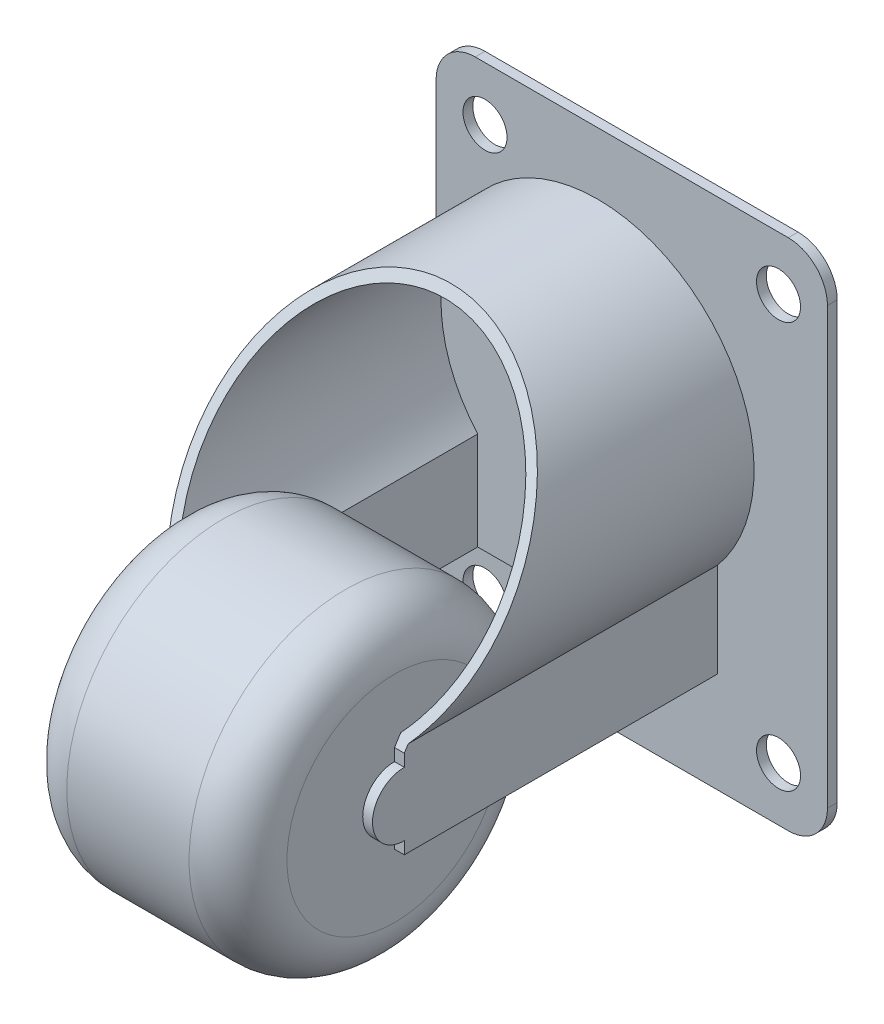
SolidWorks part; units mm, degrees
ref_plane "前视基准面" through (0, 0, 0) normal (0, 0, 1) x (1, 0, 0)
ref_plane "上视基准面" through (0, 0, 0) normal (0, 1, 0) x (1, 0, 0)
ref_plane "右视基准面" through (0, 0, 0) normal (1, 0, 0) x (0, 0, -1)
sketch "草图1" plane through (0, 0, 0) normal (0, 0, 1) x (1, 0, 0)
  line L0 (0, 0) -> (0, 20)
  line L1 (22.5, 39.8431) -> (22.5, 27.5869) construction
  line L2 (45, 0) -> (45, 20)
  line L3 (0, 0) -> (45, 0) construction
  arc A0 (0, 20) -> (45, 20) centre (22.5, 39.8431) cw
  point P7 (22.5, 69.8431)
  dimension "D1" = 30
  dimension "D2" = 45
  dimension "D3" = 20
extrude "拉伸-薄壁1" add sketch "草图1" along normal blind 62 thin thin type one direction wall 2
sketch "草图2" plane through (47, 0, 0) normal (1, 0, 0) x (0, 0, -1)
  line L1 (-62, 18) -> (-25, 76.4254)
  line L2 (-62, 0) -> (-62, 19.2579) construction
  line L7 (-25, 76.4254) -> (-62, 71.8431)
  line L8 (-62, 71.8431) -> (-62, 18)
  line L9 (-62, 0) -> (0, 0) construction
  line L10 (0, 19.2579) -> (0, 71.8431) construction
  point P7 (-29.9527, 57.8972)
  point P11 (-25, 76.4254)
  dimension "D1" = 18
  dimension "D2" = 25
extrude "切除-拉伸1" cut sketch "草图2" against normal through all both and the other way through all
ref_plane "基准面1" through (22.5, 0, 0) normal (1, 0, 0) x (0, 0, -1)
sketch "草图3" plane through (22.5, 0, 0) normal (1, 0, 0) x (0, 0, -1)
  line L0 (-62, 0) -> (-62, 18) construction
  circle A0 centre (-62, 9) radius 32
  dimension "D1" = 64
extrude "凸台-拉伸1" add sketch "草图3" along normal blind 22.5 and the other way blind 22.5 separate body
fillet "圆角1" radius 10 2 edges at (0, 9, 30) (45, 9, 30)
sketch "草图4" plane through (47, 0, 0) normal (1, 0, 0) x (0, 0, -1)
  line L0 (-62, 0) -> (-62, 18) construction
  circle A0 centre (-62, 9) radius 6.5
  dimension "D1" = 13
extrude "凸台-拉伸2" add sketch "草图4" against normal up to surface (49 mm away) up to face at (-2, 11.3032, 37.0407)
sketch "草图5" plane through (0, 0, 0) normal (0, 0, -1) x (-1, 0, 0)
  line L6 (2, 0) -> (2, 19.2579)
  line L7 (-47, 19.2579) -> (-47, 0)
  line L8 (-47, 0) -> (-45, 0)
  line L9 (-45, 0) -> (-45, 20)
  line L10 (0, 20) -> (0, 0)
  line L11 (0, 0) -> (2, 0)
  line L12 (2, 0) -> (2, 19.2579)
  line L13 (-47, 19.2579) -> (-47, 0)
  line L14 (-47, 0) -> (2, 0)
  arc A2 (2, 19.2579) -> (-47, 19.2579) centre (-22.5, 39.8431) ccw
  arc A3 (0, 20) -> (-45, 20) centre (-22.5, 39.8431) ccw
  arc A4 (2, 19.2579) -> (-47, 19.2579) centre (-22.5, 39.8431) ccw
  dimension "D1" = 0
extrude "凸台-拉伸3" add sketch "草图5" along normal blind 2
sketch "草图6" plane through (0, 0, -2) normal (0, 0, -1) x (-1, 0, 0)
  line L0 (-22.5, 71.8431) -> (-22.5, 0) construction
  line L1 (-47, 0) -> (2, 0) construction
  arc A0 (2, 19.2579) -> (-47, 19.2579) centre (-22.5, 39.8431) ccw construction
  circle A1 centre (-22.5, 25) radius 10
  dimension "D1" = 20
  dimension "D2" = 25
extrude "凸台-拉伸4" add sketch "草图6" along normal blind 7
sketch "草图7" plane through (0, 0, -9) normal (0, 0, -1) x (-1, 0, 0)
  line L1 (-62.5, -27.5) -> (17.5, -27.5)
  line L2 (-62.5, -27.5) -> (-62.5, 77.5)
  line L3 (-62.5, 77.5) -> (17.5, 77.5)
  line L4 (17.5, -27.5) -> (17.5, 77.5)
  line L5 (-62.5, -27.5) -> (17.5, 77.5) construction
  line L6 (-62.5, 77.5) -> (17.5, -27.5) construction
  point P0 (-22.5, 25)
  dimension "D1" = 105
  dimension "D2" = 80
extrude "凸台-拉伸5" add sketch "草图7" along normal blind 2
sketch "草图8" plane through (0, 0, -11) normal (0, 0, -1) x (-1, 0, 0)
  circle A0 centre (-22.5, 25) radius 90 construction
  dimension "D1" = 180
sketch "草图13" plane through (0, 0, -11) normal (0, 0, -1) x (-1, 0, 0)
  line L0 (-62.5, 25) -> (17.5, 25) construction
  line L1 (-62.5, 77.5) -> (-62.5, -27.5) construction
  line L2 (17.5, -27.5) -> (17.5, 77.5) construction
  line L4 (-52.5, -16.5) -> (7.5, -16.5) construction
  line L5 (-52.5, -16.5) -> (-52.5, 66.5) construction
  line L6 (-52.5, 66.5) -> (7.5, 66.5) construction
  line L7 (7.5, -16.5) -> (7.5, 66.5) construction
  line L8 (-52.5, -16.5) -> (7.5, 66.5) construction
  line L9 (-52.5, 66.5) -> (7.5, -16.5) construction
  circle A0 centre (-52.5, 66.5) radius 4.5
  circle A1 centre (7.5, 66.5) radius 4.5
  circle A2 centre (7.5, -16.5) radius 4.5
  circle A3 centre (-52.5, -16.5) radius 4.5
  point P6 (-22.5, 25)
  dimension "D1" = 9
  dimension "D2" = 83
  dimension "D3" = 60
extrude "切除-拉伸3" cut sketch "草图13" against normal blind 2
fillet "圆角2" radius 8 4 edges at (62.5, 77.5, -10) (-17.5, 77.5, -10) (62.5, -27.5, -10) (-17.5, -27.5, -10)
sketch "草图15" plane through (47, 0, 0) normal (1, 0, 0) x (0, 0, -1)
  line L0 (11, -65) -> (11, 115) construction
  circle A0 centre (-62, 9) radius 32 construction
  point P0 (-94, 9)
  dimension "D1" = 105
